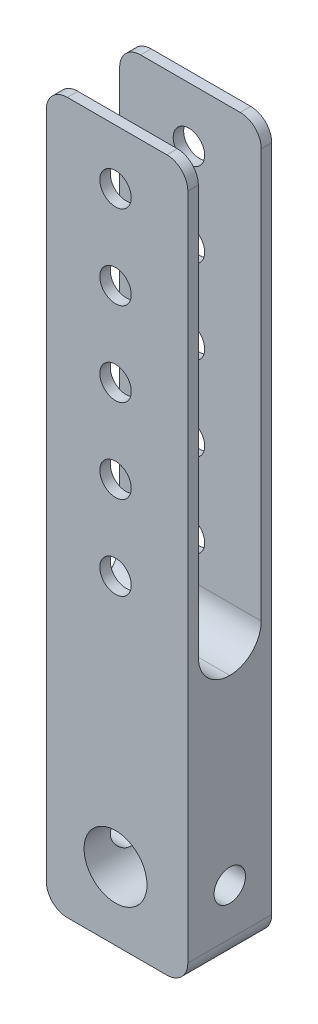
SolidWorks part; units mm, degrees
ref_plane "Front Plane" through (0, 0, 0) normal (0, 0, 1) x (1, 0, 0)
ref_plane "Top Plane" through (0, 0, 0) normal (0, 1, 0) x (1, 0, 0)
ref_plane "Right Plane" through (0, 0, 0) normal (1, 0, 0) x (0, 0, -1)
sketch "Sketch1" plane through (0, 0, 0) normal (0, 0, 1) x (1, 0, 0)
  line L1 (0, 0) -> (21.4312, 0)
  line L2 (0, 0) -> (0, 107.5531)
  line L3 (0, 107.5531) -> (21.4312, 107.5531)
  line L4 (21.4312, 0) -> (21.4312, 107.5531)
  circle A0 centre (10.4846, 10.3187) radius 4.7625
  circle A1 centre (10.4846, 99.2188) radius 2.3812
  circle A2 centre (10.4846, 86.5187) radius 2.3812
  circle A3 centre (10.4846, 73.8188) radius 2.3812
  circle A4 centre (10.4846, 61.1188) radius 2.3812
  circle A5 centre (10.4846, 48.4188) radius 2.3812
  dimension "D3" = 9.525
  dimension "D5" = 4.7625
  dimension "D6" = 8.3344
  dimension "D7" = 4.7625
  dimension "D8" = 12.7
  dimension "D9" = 4.7625
  dimension "D10" = 4.7625
  dimension "D11" = 4.7625
  dimension "D12" = 12.7
  dimension "D13" = 12.7
  dimension "D14" = 12.7
  dimension "D1" = 107.5531
  dimension "D2" = 21.4312
  dimension "D4" = 10.3187
extrude "Boss-Extrude3" add sketch "Sketch1" along normal blind 12.7
fillet "Fillet1" radius 3.175 1 edges at (21.4312, 0, 6.35)
fillet "Fillet2" radius 3.175 1 edges at (0, 0, 6.35)
fillet "Fillet3" radius 3.175 1 edges at (21.4312, 107.5531, 6.35)
fillet "Fillet4" radius 3.175 1 edges at (0, 107.5531, 6.35)
sketch "Sketch3" plane through (0, 0, 0) normal (1, 0, 0) x (0, 0, -1)
  line L0 (-12.7, 107.5531) -> (0, 107.5531) construction
  line L1 (-11.1125, 107.5531) -> (-1.5875, 107.5531)
  line L2 (-11.1125, 107.5531) -> (-11.1125, 37.7031)
  line L3 (-11.1125, 37.7031) -> (-1.5875, 37.7031)
  line L4 (-1.5875, 107.5531) -> (-1.5875, 37.7031)
  line L5 (-12.7, 3.175) -> (-12.7, 104.3781) construction
  dimension "D1" = 9.525
  dimension "D2" = 1.5875
  dimension "D3" = 69.85
extrude "Cut-Extrude2" cut sketch "Sketch3" along normal blind 21.4312 contours L2 L1 L4 L3
fillet "Fillet5" radius 4.7625 1 edges at (10.7156, 37.7031, 1.5875)
fillet "Fillet6" radius 4.7625 1 edges at (10.7156, 37.7031, 11.1125)
sketch "Sketch5" plane through (0, 0, 0) normal (1, 0, 0) x (0, 0, -1)
  line L2 (0, 0) -> (-12.7, 0) construction
  line L3 (0, 3.175) -> (0, 104.3781) construction
  circle A1 centre (-6.35, 10.2044) radius 2.3813
  dimension "D1" = 4.7625
  dimension "D3" = 6.35
  dimension "D2" = 10.2044
extrude "Cut-Extrude3" cut sketch "Sketch5" along normal blind 21.4312
